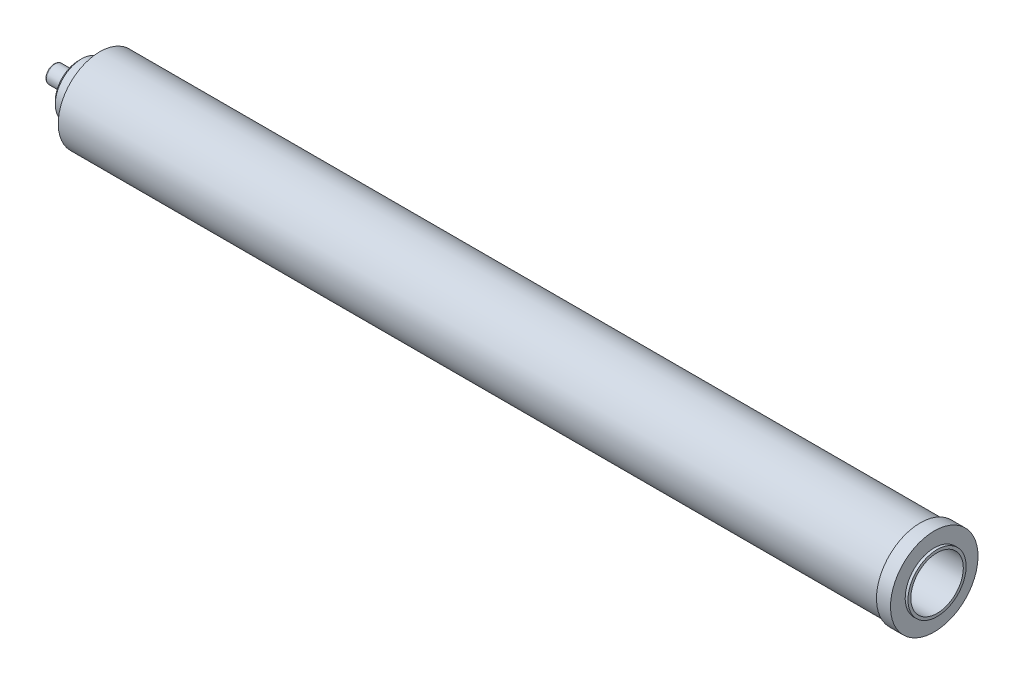
SolidWorks part; units mm, degrees
material "6061 Alloy"
ref_plane "Front Plane" through (0, 0, 0) normal (0, 0, 1) x (1, 0, 0)
ref_plane "Top Plane" through (0, 0, 0) normal (0, 1, 0) x (1, 0, 0)
ref_plane "Right Plane" through (0, 0, 0) normal (1, 0, 0) x (0, 0, -1)
sketch "Sketch1" plane through (0, 0, 0) normal (0, 0, 1) x (1, 0, 0)
  line L0 (0, 0) -> (0, 7.9502)
  line L1 (0, 7.9502) -> (25.4, 7.9502)
  line L2 (25.4, 7.9502) -> (25.4, 23.8125)
  line L3 (25.4, 23.8125) -> (44.45, 23.8125)
  line L4 (44.45, 23.8125) -> (44.45, 37.6555)
  line L5 (44.45, 37.6555) -> (788.416, 37.6555)
  line L6 (788.416, 37.6555) -> (788.416, 39.6875)
  line L7 (788.416, 39.6875) -> (801.116, 39.6875)
  line L8 (801.116, 39.6875) -> (801.116, 0)
  line L9 (801.116, 0) -> (0, 0)
  dimension "D1" = 25.4
  dimension "D2" = 23.8125
  dimension "D3" = 7.9502
  dimension "D4" = 44.45
  dimension "D5" = 743.966
  dimension "D6" = 12.7
  dimension "D7" = 39.6875
  dimension "D8" = 37.6555
revolve "Revolve1" add sketch "Sketch1" angle 360 about L9
chamfer "Chamfer1" distance 2.54 angle 45 1 edges at (25.4, 23.8125, 0)
hole_wizard "CSK for 3/8 Flat Head Machine Screw (100)1" positions "Sketch3" profile "Sketch4" countersink size "3/8" standard "ANSI Inch"
sketch "Sketch3" plane through (0, 0, 0) normal (-1, 0, 0) x (0, 0, 1)
  point P0 (0, 0)
sketch "Sketch4" plane through (0, 0, 0) normal (0, 1, 0) x (0, 0, 1)
  line L0 (0, 0) -> (0, 28.4295)
  line L1 (0, 28.4295) -> (5.0419, 25.4)
  line L2 (5.0419, 25.4) -> (5.0419, 3.8896)
  line L3 (5.0419, 3.8896) -> (9.6774, 0)
  line L5 (9.6774, 0) -> (0, 0)
  line L6 (-5.0419, 3.8896) -> (-9.6774, 0) construction
  line L10 (0, 28.4295) -> (-5.0419, 25.4) construction
  line L11 (0, -6.35) -> (0, 107.95) construction
  dimension "Hole Dia." = 10.0838
  dimension "Hole Depth" = 25.4
  dimension "Near C'Sink Dia." = 19.3548
  dimension "Near C'Sink Angle" = 100
  dimension "Drill Angle" = 118
fillet "Fillet2" radius 1.27 1 edges at (1.4493, 0, 7.9502)
sketch "Sketch5" plane through (801.116, 0, 0) normal (1, 0, 0) x (0, 0, -1)
  circle A0 centre (0, 0) radius 23.8125
  circle A1 centre (0, 0) radius 26.3525
  dimension "D1" = 47.625
  dimension "D2" = 2.54
extrude "Boss-Extrude1" add sketch "Sketch5" along normal blind 2.54
sketch "Sketch6" plane through (803.656, 0, 0) normal (1, 0, 0) x (0, 0, -1)
  circle A0 centre (0, 0) radius 23.8125
extrude "Cut-Extrude1" cut sketch "Sketch6" against normal blind 508
